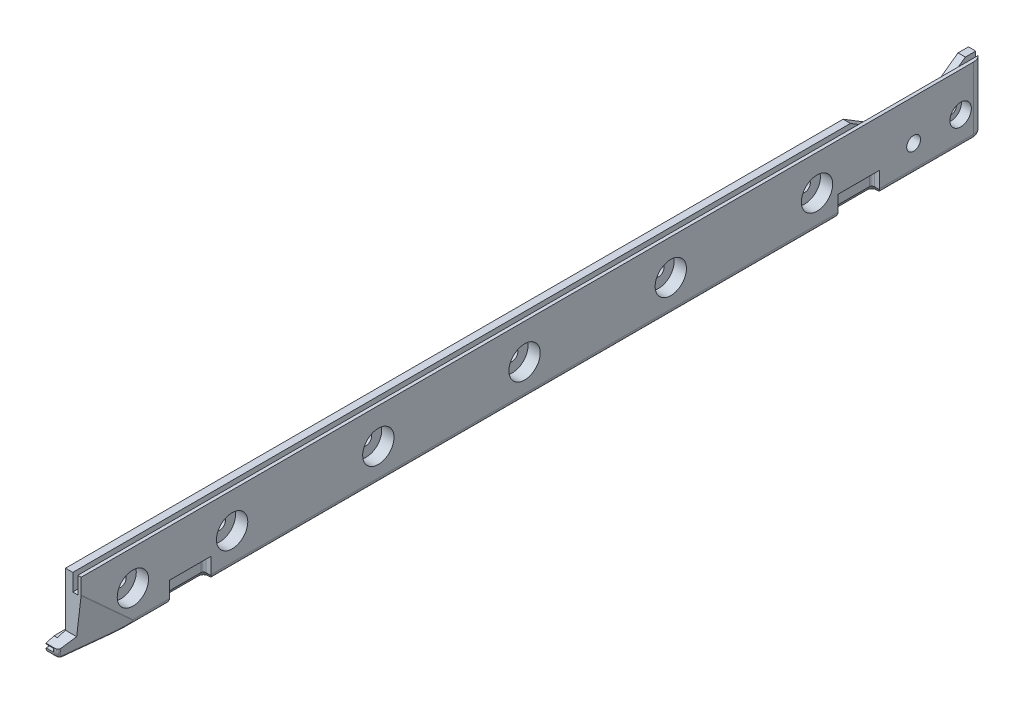
SolidWorks part; units mm, degrees
material "Delrin 2700 NC010, Low Viscosity Acetal Copolymer (SS)"
ref_plane "Front Plane" through (0, 0, 0) normal (0, 0, 1) x (1, 0, 0)
ref_plane "Top Plane" through (0, 0, 0) normal (0, 1, 0) x (1, 0, 0)
ref_plane "Right Plane" through (0, 0, 0) normal (1, 0, 0) x (0, 0, -1)
sketch "Sketch1" plane through (0, 0, 0) normal (0, 0, 1) x (1, 0, 0)
  line L0 (0, 9.1948) -> (0, 0)
  line L1 (0, -13.2224) -> (0, 13.2224) construction
  line L2 (1.27, -1.9812) -> (-1.016, -1.9812)
  line L3 (-1.016, -1.9812) -> (-1.016, -3.5052)
  line L4 (-1.016, -3.5052) -> (4.7625, -3.5052)
  line L5 (4.7625, -3.5052) -> (4.7625, 9.1948)
  line L6 (4.7625, 9.1948) -> (0, 9.1948)
  line L8 (0, 0) -> (-1.016, 0)
  line L9 (1.27, -0.9398) -> (1.27, -1.9812)
  line L10 (1.27, -0.9398) -> (-1.016, -0.9398)
  line L11 (-1.016, -0.9398) -> (-1.016, 0)
  dimension "D1" = 1.0414
  dimension "D2" = 2.286
  dimension "D3" = 1.524
  dimension "D4" = 3.5052
  dimension "D5" = 4.7625
  dimension "D6" = 1.016
  dimension "D7" = 12.7
  dimension "D8" = 0.9398
extrude "Boss-Extrude1" add sketch "Sketch1" along normal mid plane 279.4
hole_wizard "M3 Clearance Hole1" positions "Sketch3" profile "Sketch2" hole size "M3" standard "ANSI Metric" end condition up to next
sketch "Sketch3" plane through (4.7625, 0, 0) normal (1, 0, 0) x (0, 0, -1)
  line L0 (0, 21.52) -> (0, -14.8741) construction
  line L2 (3.1782, 0) -> (-3.1782, 0) construction
  point P0 (-88.9, 6.35)
  point P2 (0, 6.35)
  point P11 (88.9, 6.35)
  point P14 (-44.45, 6.35)
  point P19 (44.45, 6.35)
  dimension "D1" = 88.9
  dimension "D2" = 6.35
  dimension "D3" = 44.45
sketch "Sketch2" plane through (4.7625, 6.35, 88.9) normal (0, 1, 0) x (0, 0, -1)
  line L0 (0, 0) -> (0, 4.7625)
  line L1 (0, 4.7625) -> (1.7, 4.7625)
  line L2 (1.7, 4.7625) -> (1.7, 0)
  line L5 (1.7, 0) -> (0, 0)
  line L11 (0, -6.35) -> (0, 107.95) construction
  dimension "Thru Hole Dia." = 3.4
  dimension "Thru Hole Depth" = 4.7625
sketch "Sketch12" plane through (0, 9.1948, 0) normal (0, 1, 0) x (1, 0, 0)
  line L0 (0, -139.7) -> (0, 139.7) construction
  line L1 (0, -114.3) -> (4.7625, -114.3)
  line L2 (0, -114.3) -> (0, 139.7)
  line L3 (0, 139.7) -> (4.7625, 139.7)
  line L4 (4.7625, -114.3) -> (4.7625, 139.7)
  line L5 (4.7625, -139.7) -> (0, -139.7) construction
  line L7 (4.7625, -139.7) -> (4.7625, 139.7) construction
  line L8 (4.7625, 139.7) -> (0, 139.7) construction
  point P8 (2.3813, -139.7)
  dimension "D1" = 25.4
extrude "Boss-Extrude2" add sketch "Sketch12" along normal blind 7.874
fillet "Fillet1" radius 3.175 2 edges at (4.7625, 6.7818, -139.7) (4.7625, 2.8448, 139.7)
sketch "Sketch4" plane through (4.7625, 0, 0) normal (1, 0, 0) x (0, 0, -1)
  line L4 (0, 18.3118) -> (0, -14.4664) construction
  circle A0 centre (0, 6.35) radius 4.7625
  dimension "D1" = 9.525
extrude "Cut-Extrude1" cut sketch "Sketch4" against normal blind 3.7338
sketch "Sketch7" plane through (4.7625, 0, 0) normal (1, 0, 0) x (0, 0, -1)
  line L0 (-136.525, -3.5052) -> (136.525, -3.5052) construction
  line L1 (-107.95, -3.5052) -> (-95.25, -3.5052)
  line L2 (-107.95, -3.5052) -> (-107.95, 2.8448)
  line L3 (-107.95, 2.8448) -> (-95.25, 2.8448)
  line L4 (-95.25, -3.5052) -> (-95.25, 2.8448)
  line L5 (0, 15.7835) -> (0, -19.0435) construction
  line L6 (-101.6, -3.5052) -> (-101.6, 6.0395) construction
  line L7 (95.25, -3.5052) -> (95.25, 2.8448)
  line L8 (107.95, 2.8448) -> (95.25, 2.8448)
  line L9 (107.95, -3.5052) -> (107.95, 2.8448)
  line L10 (107.95, -3.5052) -> (95.25, -3.5052)
  dimension "D1" = 12.7
  dimension "D2" = 6.35
  dimension "D3" = 101.6
extrude "Cut-Extrude2" cut sketch "Sketch7" against normal blind 2.3813
fillet "Fillet4" radius 0.762 4 edges at (2.3812, -0.3302, 95.25) (2.3812, -0.3302, 107.95) (2.3812, -0.3302, -95.25) (2.3812, -0.3302, -107.95)
chamfer "Chamfer3" distance 1.1906 angle 30 10 edges at (3.9529, -3.5052, 107.95) (3.9529, -3.5052, 95.25) (2.6044, -3.5052, 95.4732) (2.3812, -3.5052, 101.6) (2.6044, -3.5052, 107.7268) (3.9529, -3.5052, -95.25) (3.9529, -3.5052, -107.95) (2.6044, -3.5052, -107.7268) (2.3812, -3.5052, -101.6) (2.6044, -3.5052, -95.4732)
pattern_linear "LPattern1" count 3 spacing 44.45 along (0, 0, 1) count 3 spacing 44.45 along (0, 0, -1) of "Cut-Extrude1"
sketch "Sketch8" plane through (4.7625, 0, 0) normal (1, 0, 0) x (0, 0, -1)
  line L0 (-139.7, -0.7271) -> (-114.3, 6.8324)
  line L1 (-139.7, 9.1948) -> (-114.3, 9.1948)
  line L2 (-139.7, 9.1948) -> (-139.7, -0.7271)
  line L3 (-139.7, -3.5052) -> (-136.525, -3.5052) construction
  line L4 (-114.3, 9.1948) -> (-114.3, 6.8324)
  dimension "D1" = 73.426
  dimension "D2" = 2.7781
extrude "Cut-Extrude3" cut sketch "Sketch8" against normal through all
hole_wizard "CBORE for M3 SHCS2" positions "Sketch10" profile "Sketch11" counterbore size "M3" standard "ANSI Metric" end condition through all
sketch "Sketch10" plane through (4.7625, 0, 0) normal (1, 0, 0) x (0, 0, -1)
  line L0 (139.7, 17.0688) -> (139.7, -3.5052) construction
  line L1 (108.6374, -3.5052) -> (136.525, -3.5052) construction
  point P0 (132.5562, 5.1943)
  dimension "D1" = 7.1438
  dimension "D2" = 8.6995
sketch "Sketch11" plane through (4.7625, 5.1943, -132.5562) normal (0, 1, 0) x (0, 0, -1)
  line L0 (0, 0) -> (0, 5.7785)
  line L1 (0, 5.7785) -> (1.7, 5.7785)
  line L3 (1.7, 5.7785) -> (1.7, 3)
  line L4 (1.7, 3) -> (3.25, 3)
  line L5 (3.25, 3) -> (3.25, 0)
  line L7 (3.25, 0) -> (0, 0)
  line L11 (0, -6.35) -> (0, 107.95) construction
  dimension "Thru Hole Dia." = 3.4
  dimension "Thru Hole Depth" = 5.7785
  dimension "C'Bore Dia." = 6.5
  dimension "C'Bore Depth" = 3
sketch "Sketch16" plane through (4.7625, 0, 0) normal (1, 0, 0) x (0, 0, -1)
  line L0 (-114.3, 17.0688) -> (-134.797, 17.0688)
  line L1 (-134.797, 17.0688) -> (-134.797, 0.7322)
  line L2 (-136.525, 0.2179) -> (-114.3, 6.8324) construction
  line L3 (-134.797, 0.7322) -> (-114.3, 6.8324)
  line L4 (-114.3, 6.8324) -> (-114.3, 17.0688)
extrude "Boss-Extrude3" add sketch "Sketch16" against normal up to surface (4.7625 mm away) up to face at (0, 6.8943, -132.5562)
sketch "Sketch13" plane through (0, 17.0688, 0) normal (0, 1, 0) x (1, 0, 0)
  line L1 (0, -134.797) -> (4.7625, -134.797) construction
  line L2 (3.7465, -134.797) -> (2.2225, -134.797)
  line L3 (3.7465, -134.797) -> (3.7465, 139.7)
  line L4 (3.7465, 139.7) -> (2.2225, 139.7)
  line L5 (2.2225, -134.797) -> (2.2225, 139.7)
  line L6 (1.5875, 139.7) -> (0, 139.7) construction
  line L7 (4.7625, -134.797) -> (4.7625, 136.525) construction
  dimension "D1" = 1.016
  dimension "D2" = 1.524
extrude "Cut-Extrude5" cut sketch "Sketch13" against normal blind 5.1594
sketch "Sketch15" plane through (0, 0, 0) normal (-1, 0, 0) x (0, 0, 1)
  line L0 (-111.9187, 10.7506) -> (-101.6, 17.0688)
  line L1 (-139.7, 17.0688) -> (134.797, 17.0688) construction
  line L2 (-101.6, 17.0688) -> (-136.525, 17.0688)
  line L3 (139.7, -3.5052) -> (-139.7, -3.5052) construction
  line L4 (-139.7, 17.0688) -> (-139.7, 0) construction
  line L5 (-111.9187, 10.7506) -> (-127.7937, 10.7505)
  line L7 (-139.7, 17.0688) -> (134.797, 17.0688) construction
  line L8 (-139.7, -1.9812) -> (-139.7, -3.5052) construction
  line L9 (-127.7937, 10.7505) -> (-136.525, 17.0688)
  line L10 (-139.7, 17.0688) -> (134.797, 17.0688) construction
  point P18 (-139.7, -2.7432)
  dimension "D1" = 38.1
  dimension "D2" = 27.7813
  dimension "D3" = 14.2558
  dimension "D4" = 11.9062
  dimension "D5" = 3.175
extrude "Cut-Extrude6" cut sketch "Sketch15" against normal blind 2.3622
fillet "Fillet8" radius 1.524 7 edges at (0.2858, -3.5052, 139.7) (3.8326, -3.5052, 138.7701) (0.2858, -3.5052, -139.7) (3.8326, -3.5052, -138.7701) (4.7625, -3.5052, 122.5812) (4.7625, -3.5052, -122.5812) (4.7625, -3.5052, 0)
fillet "Fillet9" radius 1.5875 2 edges at (1.1811, 10.7505, -127.7937) (1.1811, 10.7506, -111.9187)
hole_wizard "M3 Clearance Hole2" positions "Sketch17" profile "Sketch18" hole size "M3" standard "ANSI Metric" end condition up to next
sketch "Sketch17" plane through (4.7625, 0, 0) normal (1, 0, 0) x (0, 0, -1)
  point P0 (-119.0625, 6.35)
  dimension "D1" = 30.1625
sketch "Sketch18" plane through (4.7625, 6.35, 119.0625) normal (0, 1, 0) x (0, 0, -1)
  line L0 (0, 0) -> (0, 4.7625)
  line L1 (0, 4.7625) -> (1.7, 4.7625)
  line L2 (1.7, 4.7625) -> (1.7, 0)
  line L5 (1.7, 0) -> (0, 0)
  line L11 (0, -6.35) -> (0, 107.95) construction
  dimension "Thru Hole Dia." = 3.4
  dimension "Thru Hole Depth" = 4.7625
sketch "Sketch19" plane through (4.7625, 0, 0) normal (1, 0, 0) x (0, 0, -1)
  circle A0 centre (-119.0625, 6.35) radius 4.7625
  dimension "D1" = 9.525
extrude "Cut-Extrude7" cut sketch "Sketch19" against normal up to surface (3.7338 mm away) up to face at (1.0287, 11.1125, 88.9)
sketch "Sketch20" plane through (0, -3.5052, 0) normal (0, -1, 0) x (1, 0, 0)
  line L0 (4.7625, 117.475) -> (4.7625, 139.7)
  line L1 (4.7625, 136.525) -> (4.7625, 107.95) construction
  line L2 (4.7625, 139.7) -> (2.3813, 139.7)
  line L3 (2.3813, 139.7) -> (4.7625, 117.475)
  line L6 (1.27, 139.7) -> (-1.016, 139.7) construction
  dimension "D1" = 22.225
  dimension "D2" = 2.3813
sketch "Sketch22" plane through (4.7625, 0, 0) normal (1, 0, 0) x (0, 0, -1)
  line L0 (-134.797, 17.0688) -> (-134.797, 0.7322) construction
  line L1 (-134.797, 17.0688) -> (136.525, 17.0688) construction
  point P0 (-134.797, 12.3063)
  dimension "D1" = 4.7625
ref_plane "Plane1" through (17.323, -2.0333, 1.856) normal (0.9876, -0.1159, 0.1058) x (0.1043, -0.019, -0.9944)
sketch "Sketch21" plane through (17.323, -2.0333, 1.856) normal (0.9876, -0.1159, 0.1058) x (0.1043, -0.019, -0.9944)
  line L1 (-140.0611, -4.8312) -> (-117.2011, -4.8312)
  line L2 (-140.0611, -4.8312) -> (-140.0611, 15.4888)
  line L3 (-140.0611, 15.4888) -> (-117.2011, 15.4888)
  line L4 (-117.2011, -4.8312) -> (-117.2011, 15.4888)
  dimension "D1" = 20.32
  dimension "D2" = 22.86
  dimension "D3" = 6.2872
  dimension "D4" = 0.7011
extrude "Cut-Extrude8" cut sketch "Sketch21" along normal through all
fillet "Fillet10" radius 0.762 5 edges at (4.7625, 5.1626, 126.9708) (4.3161, -3.0588, 122.1301) (2.9093, -3.5052, 134.7717) (2.5028, -2.8585, 139.2737) (2.6579, -1.3177, 139.5141)
hole_wizard "M5x0.8 Tapped Hole1" positions "Sketch24" profile "Sketch25" tap size "M5x0.8" standard "ANSI Metric" end condition up to next
sketch "Sketch24" plane through (4.7625, 0, 0) normal (1, 0, 0) x (0, 0, -1)
  line L0 (139.7, 17.0688) -> (139.7, -1.9812) construction
  line L2 (136.525, -3.5052) -> (108.6374, -3.5052) construction
  point P0 (118.2687, 4.7625)
  dimension "D1" = 21.4312
  dimension "D2" = 8.2677
cosmetic thread "Hole Thread1" parameters "D2"=5
sketch "Sketch25" plane through (4.7625, 4.7625, -118.2687) normal (0, 1, 0) x (0, 0, -1)
  line L0 (0, 0) -> (0, 4.7625)
  line L1 (0, 4.7625) -> (2.1, 4.7625)
  line L2 (2.1, 4.7625) -> (2.1, 0)
  line L5 (2.1, 0) -> (0, 0)
  line L11 (0, -6.35) -> (0, 107.95) construction
  dimension "Thru Tap Drill Dia." = 4.2
  dimension "Thru Tap Drill Depth" = 4.7625
